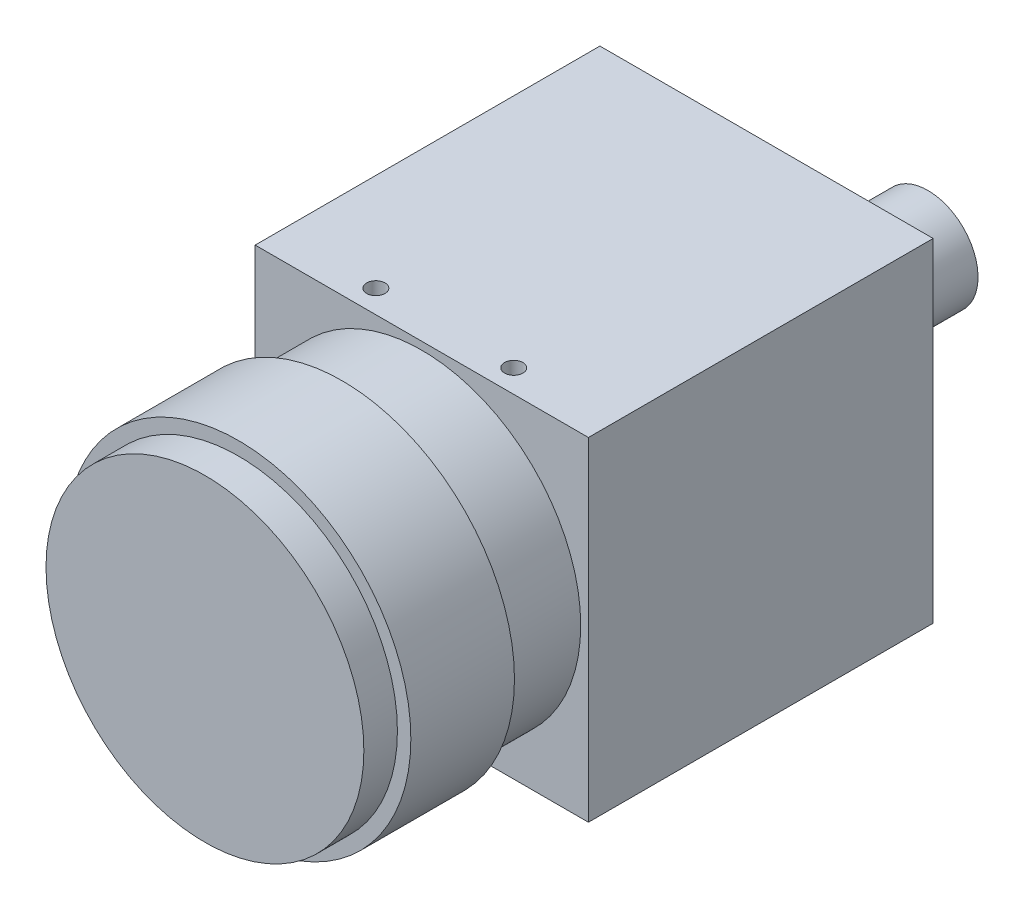
SolidWorks part; units mm, degrees
ref_plane "Front Plane" through (0, 0, 0) normal (0, 0, 1) x (1, 0, 0)
ref_plane "Top Plane" through (0, 0, 0) normal (0, 1, 0) x (1, 0, 0)
ref_plane "Right Plane" through (0, 0, 0) normal (1, 0, 0) x (0, 0, -1)
sketch "Sketch1" plane through (0, 0, 0) normal (0, 0, 1) x (1, 0, 0)
  line L1 (0, 0) -> (29, 0)
  line L2 (0, 0) -> (0, 29)
  line L3 (0, 29) -> (29, 29)
  line L4 (29, 0) -> (29, 29)
  dimension "D1" = 29
  dimension "D2" = 29
extrude "Boss-Extrude1" add sketch "Sketch1" along normal blind 30
sketch "Sketch2" plane through (0, 0, 30) normal (0, 0, 1) x (1, 0, 0)
  line L5 (14.5, 29) -> (14.5, 0) construction
  line L6 (29, 29) -> (0, 29) construction
  line L7 (0, 0) -> (29, 0) construction
  line L8 (0, 14.5) -> (29, 14.5) construction
  line L9 (0, 29) -> (0, 0) construction
  line L10 (29, 0) -> (29, 29) construction
  circle A0 centre (14.5, 14.5) radius 13.8303
  circle A1 centre (14.5, 14.5) radius 14.9987
  dimension "D1" = 27.6606
  dimension "D2" = 29.9974
extrude "Boss-Extrude2" add sketch "Sketch2" along normal blind 18.8722 contours A0
hole_wizard "M2x0.4 Tapped Hole1" positions "Sketch8" profile "Sketch9" tap size "M2x0.4" standard "ANSI Metric"
sketch "Sketch8" plane through (0, 0, 0) normal (0, -1, 0) x (-1, 0, 0)
  line L1 (-20.5, -3.5) -> (-14.5, -3.5) construction
  line L2 (-20.5, -3.5) -> (-20.5, -25.5) construction
  line L3 (-20.5, -25.5) -> (-14.5, -25.5) construction
  line L6 (0, -30) -> (-29, -30) construction
  line L12 (-14.5, -30) -> (-14.5, 0) construction
  line L13 (0, 0) -> (-29, 0) construction
  line L15 (-8.5, -3.5) -> (-8.5, -25.5) construction
  line L16 (0, -30) -> (-29, -30) construction
  point P1 (-20.5, -3.5)
  point P59 (-20.5, -25.5)
  point P87 (-8.5, -3.5)
  point P88 (-8.5, -25.5)
  dimension "D1" = 4.5
  dimension "D2" = 6
  dimension "D3" = 22
sketch "Sketch9" plane through (20.5, 0, 3.5) normal (1, 0, 0) x (0, 0, -1)
  line L0 (0, 0) -> (0, 8.7916)
  line L1 (0, 8.7916) -> (0.8, 8.3109)
  line L2 (0.8, 8.3109) -> (0.8, 0)
  line L5 (0.8, 0) -> (0, 0)
  line L10 (0, 8.7916) -> (-0.8, 8.3109) construction
  line L11 (0, -6.35) -> (0, 107.95) construction
  dimension "Tap Drill Dia." = 1.6
  dimension "Tap Drill Depth" = 8.3109
  dimension "Drill Angle" = 118
hole_wizard "M2x0.4 Tapped Hole2" positions "Sketch11" profile "Sketch10" tap size "M2x0.4" standard "ANSI Metric"
sketch "Sketch11" plane through (0, 29, 0) normal (0, 1, 0) x (1, 0, 0)
  line L0 (29, -28) -> (0, -28) construction
  line L1 (29, -30) -> (29, 0) construction
  line L2 (0, -30) -> (0, 0) construction
  line L4 (14.5, -30) -> (14.5, 0) construction
  line L5 (29, 0) -> (0, 0) construction
  line L7 (0.6697, -30) -> (28.3303, -30) construction
  line L8 (29, -30) -> (0, -30) construction
  point P0 (20.5, -28)
  point P24 (8.5, -28)
  dimension "D1" = 2
  dimension "D2" = 6
sketch "Sketch10" plane through (20.5, 29, 28) normal (1, 0, 0) x (0, 0, 1)
  line L0 (0, 0) -> (0, 8.7916)
  line L1 (0, 8.7916) -> (0.8, 8.3109)
  line L2 (0.8, 8.3109) -> (0.8, 0)
  line L5 (0.8, 0) -> (0, 0)
  line L10 (0, 8.7916) -> (-0.8, 8.3109) construction
  line L11 (0, -6.35) -> (0, 107.95) construction
  dimension "Tap Drill Dia." = 1.6
  dimension "Tap Drill Depth" = 8.3109
  dimension "Drill Angle" = 118
hole_wizard "M3x0.5 Tapped Hole1" positions "Sketch14" profile "Sketch12" tap size "M3x0.5" standard "ANSI Metric"
sketch "Sketch14" plane through (0, 0, 0) normal (0, -1, 0) x (-1, 0, 0)
  line L0 (-14.5, -30) -> (-14.5, 0) construction
  line L1 (0, 0) -> (-29, 0) construction
  line L3 (-29, -27) -> (0, -27) construction
  line L4 (-29, -30) -> (-29, 0) construction
  line L5 (0, -30) -> (0, 0) construction
  line L7 (-28.3303, -30) -> (-0.6697, -30) construction
  line L8 (0, -30) -> (-29, -30) construction
  point P18 (-14.5, -3.5)
  point P21 (-4.5, -27)
  point P25 (-24.5, -27)
  dimension "D1" = 3
  dimension "D2" = 23.5
  dimension "D3" = 10
sketch "Sketch12" plane through (14.5, 0, 3.5) normal (1, 0, 0) x (0, 0, -1)
  line L0 (0, 0) -> (0, 8.2517)
  line L1 (0, 8.2517) -> (1.25, 7.5006)
  line L2 (1.25, 7.5006) -> (1.25, 0)
  line L5 (1.25, 0) -> (0, 0)
  line L10 (0, 8.2517) -> (-1.25, 7.5006) construction
  line L11 (0, -6.35) -> (0, 107.95) construction
  dimension "Tap Drill Dia." = 2.5
  dimension "Tap Drill Depth" = 7.5006
  dimension "Drill Angle" = 118
sketch "Sketch15" plane through (0, 0, 0) normal (0, 0, -1) x (-1, 0, 0)
  line L0 (0, 0) -> (-29, 0) construction
  line L1 (-19.5724, 18.034) -> (-5.1308, 18.034)
  line L2 (-22.098, 17.2271) -> (-22.098, 3.048)
  line L3 (-22.098, 3.048) -> (-5.1308, 3.048)
  line L4 (-5.1308, 18.034) -> (-5.1308, 3.048)
  line L5 (0, 29) -> (0, 0) construction
  line L7 (-29, 29) -> (0, 29) construction
  circle A0 centre (-22.098, 21.5832) radius 4.3561
  arc A1 (-22.098, 17.2271) -> (-19.5724, 18.034) centre (-22.098, 21.5832) ccw
  dimension "D5" = 8.7122
  dimension "D1" = 14.986
  dimension "D2" = 16.9672
  dimension "D3" = 3.048
  dimension "D4" = 5.1308
  dimension "D6" = 7.4168
extrude "Boss-Extrude4" add sketch "Sketch15" along normal blind 3.937 contours A0 L2 L3 L4 L1 | A0 region at (13.5732, 10.5017, 0) region at (22.098, 21.5832, 0)
extrude "Boss-Extrude5" add sketch "Sketch15<7>" along normal blind 6.4516 contours A0
sketch "Sketch15<7>" plane through (0, 0, 0) normal (0, 0, -1) x (-1, 0, 0) same geometry as "Sketch15"
extrude "Boss-Extrude6" add sketch "Sketch2<5>" along normal blind 9.017 from offset 6.9342 contours A1
sketch "Sketch2<5>" plane through (0, 0, 30) normal (0, 0, 1) x (1, 0, 0) same geometry as "Sketch2"
